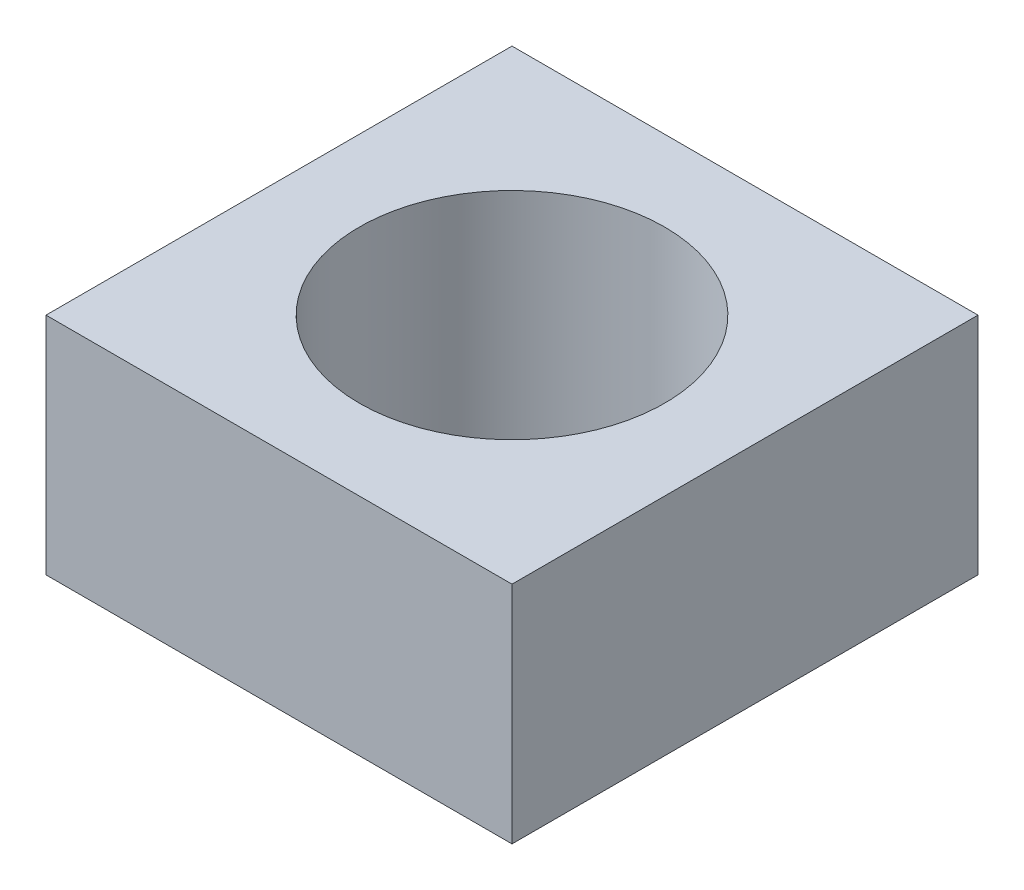
SolidWorks part; units mm, degrees
material "6061-T6 (SS)"
ref_plane "Front Plane" through (0, 0, 0) normal (0, 0, 1) x (1, 0, 0)
ref_plane "Top Plane" through (0, 0, 0) normal (0, 1, 0) x (1, 0, 0)
ref_plane "Right Plane" through (0, 0, 0) normal (1, 0, 0) x (0, 0, -1)
ref_axis "Axis1" through (0, 0, 55) along (0, 0, -1)
sketch "Sketch1" plane through (0, 0, 0) normal (0, 1, 0) x (1, 0, 0)
  line L1 (-7.25, 7.25) -> (7.25, 7.25)
  line L2 (-7.25, 7.25) -> (-7.25, -7.25)
  line L3 (-7.25, -7.25) -> (7.25, -7.25)
  line L4 (7.25, 7.25) -> (7.25, -7.25)
  line L5 (-7.25, 7.25) -> (7.25, -7.25) construction
  line L6 (-7.25, -7.25) -> (7.25, 7.25) construction
  circle A0 centre (0, 0) radius 4.75
  circle A1 centre (0, 0) radius 7.25 construction
  point P0 (0, 0)
  dimension "D2" = 9.5
  dimension "D3" = 2.5
extrude "Boss-Extrude1" add sketch "Sketch1" along normal blind 7
